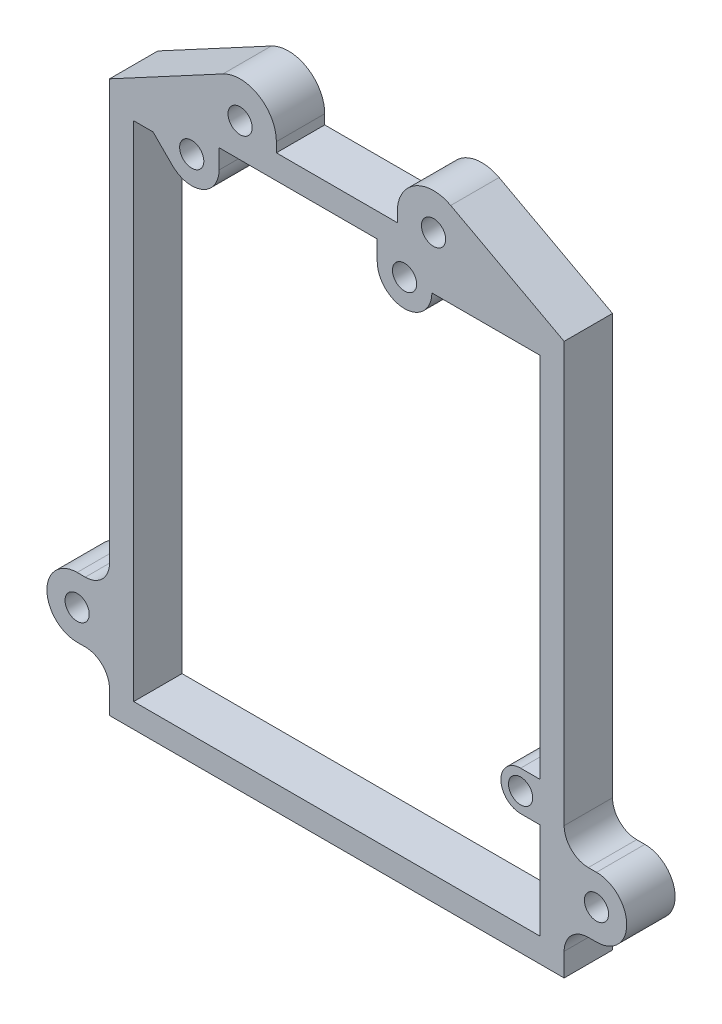
SolidWorks part; units mm, degrees
ref_plane "Front Plane" through (0, 0, 0) normal (0, 0, 1) x (1, 0, 0)
ref_plane "Top Plane" through (0, 0, 0) normal (0, 1, 0) x (1, 0, 0)
ref_plane "Right Plane" through (0, 0, 0) normal (1, 0, 0) x (0, 0, -1)
sketch "Sketch1" plane through (0, 0, 0) normal (0, 0, 1) x (1, 0, 0)
  line L0 (13.97, -3.175) -> (39.37, -3.175)
  line L2 (39.37, -3.175) -> (56.515, -3.175)
  line L3 (18.7325, 73.025) -> (18.7325, 71.755)
  line L4 (56.515, 69.215) -> (41.6251, 77.2198)
  line L5 (34.6075, 73.025) -> (34.6075, 71.755)
  line L6 (-3.175, 69.215) -> (11.7149, 77.2198)
  line L7 (34.6075, 71.755) -> (18.7325, 71.755)
  line L8 (0, 11.0938) -> (0, 16.5575)
  line L36 (53.34, 66.04) -> (53.34, 0) construction
  line L37 (53.34, 0) -> (0, 0) construction
  line L38 (0, 0) -> (0, 66.04) construction
  line L39 (0, 66.04) -> (2.54, 66.04) construction
  line L43 (40.386, 66.04) -> (53.34, 66.04) construction
  line L44 (-3.175, -3.175) -> (56.515, -3.175)
  line L45 (56.515, -3.175) -> (56.515, 69.215)
  line L46 (-3.175, 69.215) -> (-3.175, -3.175)
  line L47 (1.2249, 69.215) -> (-3.175, 69.215)
  line L48 (3.7649, 71.755) -> (1.2249, 69.215)
  line L49 (39.1611, 71.755) -> (3.7649, 71.755)
  line L50 (41.7011, 69.215) -> (39.1611, 71.755)
  line L51 (56.515, 69.215) -> (41.7011, 69.215)
  line L52 (-3.175, -3.175) -> (13.97, -3.175)
  line L53 (56.515, -3.175) -> (56.515, 69.215)
  line L54 (-3.175, 69.215) -> (-3.175, -3.175)
  line L60 (53.34, 66.04) -> (53.34, 17.8275)
  line L61 (53.34, 0) -> (0, 0)
  line L62 (0, 0) -> (0, 11.0938)
  line L63 (0, 66.04) -> (2.54, 66.04)
  line L64 (26.67, -3.175) -> (26.67, 77.2177) construction
  line L66 (11.2075, 68.58) -> (31.9725, 68.58)
  line L67 (40.386, 66.04) -> (53.34, 66.04)
  line L68 (50.8, 17.8275) -> (53.34, 17.8275)
  line L69 (50.8, 12.6525) -> (53.34, 12.6525)
  line L70 (53.34, 12.6525) -> (53.34, 0)
  line L74 (0, 16.5575) -> (0, 66.04)
  line L75 (5.08, 63.5065) -> (2.54, 66.04)
  line L76 (11.2075, 66.04) -> (11.2075, 68.58)
  line L77 (39.1475, 66.04) -> (40.386, 66.04)
  line L78 (31.9725, 66.04) -> (31.9725, 68.58)
  circle A0 centre (35.56, 66.04) radius 1.5875 construction
  circle A1 centre (7.62, 66.04) radius 1.5875 construction
  circle A3 centre (50.8, 15.24) radius 1.5875 construction
  circle A4 centre (35.56, 66.04) radius 1.5875
  circle A5 centre (7.62, 66.04) radius 1.5875
  circle A7 centre (50.8, 15.24) radius 1.5875
  arc A9 (50.8, 17.8275) -> (50.8, 12.6525) centre (50.8, 15.24) ccw
  arc A10 (5.08, 63.5065) -> (11.2075, 66.04) centre (7.62, 66.04) ccw
  arc A13 (31.9725, 66.04) -> (39.1475, 66.04) centre (35.56, 66.04) ccw
  circle A15 centre (35.56, 66.04) radius 3.5875 construction
  circle A16 centre (7.62, 66.04) radius 3.5875 construction
  circle A18 centre (39.37, 73.025) radius 1.5875
  arc A19 (41.6251, 77.2198) -> (34.6075, 73.025) centre (39.37, 73.025) ccw
  circle A20 centre (13.97, 73.025) radius 1.5875
  arc A22 (11.7149, 77.2198) -> (18.7325, 73.025) centre (13.97, 73.025) cw
  circle A24 centre (13.97, 73.025) radius 4.7625 construction
  point P20 (2.54, 13.97)
  point P29 (2.54, 13.97)
  point P34 (53.3875, 15.24)
  point P37 (6.1275, 13.97)
  point P41 (4.0581, 14.4341)
  point P47 (11.2075, 66.04)
  point P54 (39.1475, 66.04)
  point P58 (26.67, -9.525)
  point P64 (31.4325, -9.525)
  point P65 (26.67, -6.35)
  point P69 (26.67, 71.755)
  point P71 (39.37, 73.025)
  point P74 (50.4825, 73.025)
  point P75 (12.3825, 73.025)
  point P78 (31.4325, -6.35)
  dimension "D8" = 3.175
  dimension "D7" = 12.7
  dimension "D9" = 12.7
  dimension "D1" = 3.175
  dimension "D3" = 2
  dimension "D12" = 3.175
extrude "Boss-Extrude1" add sketch "Sketch1" along normal blind 6.35
sketch "Sketch3" plane through (0, 0, 6.35) normal (0, 0, 1) x (1, 0, 0)
  line L0 (26.67, 0) -> (26.67, 68.58) construction
  line L1 (0, 0) -> (53.34, 0) construction
  line L2 (31.9725, 68.58) -> (11.2075, 68.58) construction
  line L3 (-3.175, -3.175) -> (56.515, -3.175) construction
  line L4 (-3.175, 69.215) -> (-3.175, -3.175) construction
  line L5 (-7.4237, 10.9692) -> (-3.175, 10.9692)
  line L6 (-7.4237, 3.0317) -> (-3.175, 3.0317)
  line L7 (-3.175, 3.0317) -> (-3.175, 10.9692)
  line L8 (56.515, 3.0317) -> (56.515, 10.9692)
  line L9 (60.7637, 3.0317) -> (56.515, 3.0317)
  line L10 (60.7637, 10.9692) -> (56.515, 10.9692)
  circle A0 centre (-7.4237, 7.0005) radius 1.5875
  arc A1 (-7.4237, 10.9692) -> (-7.4237, 3.0317) centre (-7.4237, 7.0005) ccw
  arc A2 (60.7637, 10.9692) -> (60.7637, 3.0317) centre (60.7637, 7.0005) cw
  circle A3 centre (60.7637, 7.0005) radius 1.5875
  dimension "D1" = 3.175
  dimension "D2" = 10.1755
  dimension "D3" = 4.2487
extrude "Boss-Extrude2" add sketch "Sketch3" against normal up to surface (6.35 mm away) up to face at (26.67, 58.006, 0)
fillet "Fillet1" radius 3.175 4 edges
